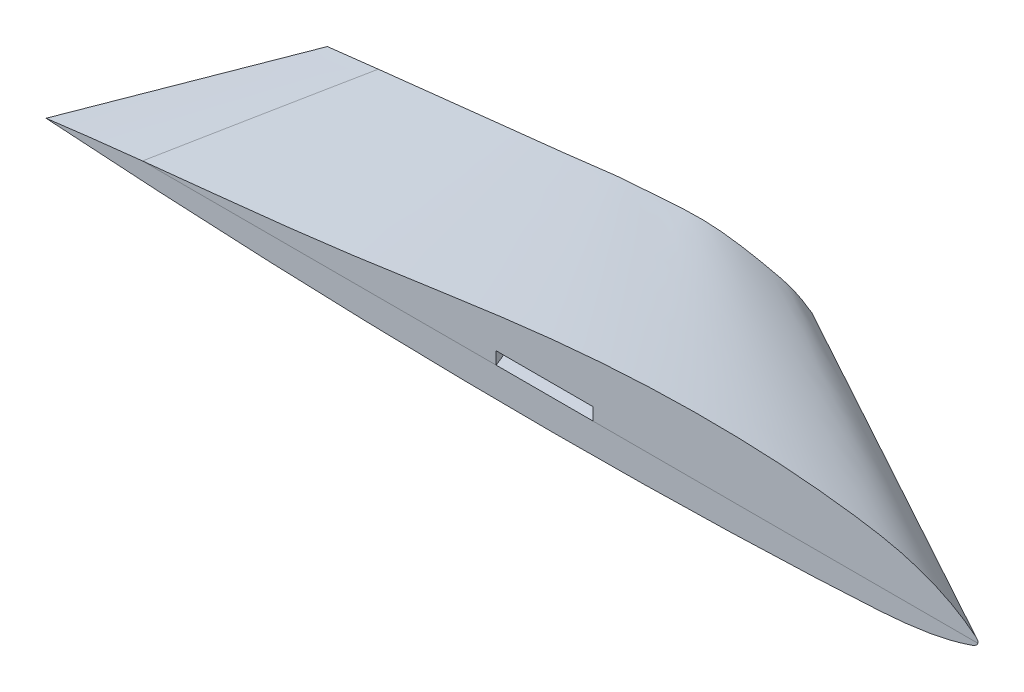
SolidWorks part; units mm, degrees
material "EPS 1.5lb"
ref_plane "Front Plane" through (0, 0, 0) normal (0, 0, 1) x (1, 0, 0)
ref_plane "Top Plane" through (0, 0, 0) normal (0, 1, 0) x (1, 0, 0)
ref_plane "Right Plane" through (0, 0, 0) normal (1, 0, 0) x (0, 0, -1)
sketch "Sketch1" plane through (0, 0, 0) normal (0, 0, 1) x (1, 0, 0)
  spline S3 degree 3 poles (-353.0971, 3.7664) (-263.6099, 15.4897) (-103.4056, 27.7025) (139.6254, 69.7319) (320.6009, 70.898) (447.0294, 49.1568) (484.462, 32.3978) (505.2254, 13.2914) knots 0 0 0 0 0.308402 0.542913 0.85017 0.887176 1 1 1 1
  spline S4 degree 3 poles (-353.0971, 3.7664) (-171.2042, -8.6227) (70.6812, -17.727) (367.6345, -8.5893) (467.935, -1.6347) (505.2254, 13.2914) knots 0 0 0 0 0.625313 0.861779 1 1 1 1
ref_plane "Plane1" through (0, 0, -180.975) normal (0, 0, 1) x (1, 0, 0)
sketch "Sketch2" plane through (0, 0, -180.975) normal (0, 0, 1) x (1, 0, 0)
  ellipse E1 centre (137.6249, -20.0426) end of major axis (189.6794, -20.0426) minor radius 48.2641 (175.2698, 13.2914) -> (153.373, 25.9598) ccw construction
  spline S0 degree 3 poles (-276.1301, 8.6931) (-231.4597, 13.8922) (-160.6069, 22.0458) (-55.2186, 32.8482) (-5.4847, 39.5878) (20.2948, 40.7341) (52.2153, 43.3112) (77.4334, 43.8548) (107.6579, 39.591) (131.1314, 34.7665) (149.4992, 30.2941) (163.4187, 23.0591) (171.5303, 16.9219) (175.2698, 13.2914) knots 0 0 0 0 0.247404 0.462109 0.504395 0.627983 0.653402 0.743134 0.818761 0.882434 0.92418 0.960505 1 1 1 1
  spline S4 degree 3 poles (-276.1301, 8.6931) (-174.261, 0.9112) (-23.6694, 0.6839) (127.5151, 0.6814) (175.2698, 13.2914) knots 0 0 0 0 0.676464 1 1 1 1
loft "Loft1" add profiles "Sketch1", "Sketch2" connector at (-353.0971, 3.7664, 0) connector at (-276.1301, 8.6931, -180.975)
fillet "Fillet1" radius 6.35 1 edges
ref_plane "Plane2" through (0, 19.812, 0) normal (0, 1, 0) x (1, 0, 0)
sketch "Sketch7" plane through (0, 19.812, 0) normal (0, 1, 0) x (1, 0, 0)
  line L0 (148.5529, 0) -> (75.4342, 180.975)
  line L1 (-13.4658, 180.975) -> (59.6529, 0)
  line L2 (59.6529, 0) -> (148.5529, 0)
  line L3 (75.4342, 180.975) -> (-13.4658, 180.975)
  line L5 (-44.6577, 180.975) -> (44.6577, 180.975) construction
  line L7 (-44.6562, 0) -> (44.6562, 0) construction
  dimension "D1" = 501.65
  dimension "D2" = 88.9
  dimension "D3" = 68
  dimension "D4" = 88.9
extrude "Cut-Extrude1" cut sketch "Sketch7" against normal mid plane 11.43
sketch "Sketch8" plane through (0, 19.812, 0) normal (0, 1, 0) x (1, 0, 0)
  line L0 (-276.1301, 180.975) -> (-353.0971, 0) construction
  line L2 (-328.3189, 58.2617) -> (-239.4979, 20.487)
  line L3 (-239.4979, 20.487) -> (-171.2438, 180.975)
  line L4 (-171.2438, 180.975) -> (-276.1301, 180.975)
  line L5 (167.9966, 180.975) -> (-276.1301, 180.975) construction
  line L6 (167.9966, 180.975) -> (-276.1301, 180.975) construction
  line L7 (-276.1301, 180.975) -> (-328.3189, 58.2617)
  dimension "D1" = 133.35
  dimension "D2" = 96.52
extrude "Cut-Extrude2" [suppressed] cut sketch "Sketch8" against normal through all and the other way through all
sketch "Sketch9" plane through (0, 0, 0) normal (0, 0, 1) x (1, 0, 0)
  line L0 (501.6041, 0) -> (501.407, 14.9983) construction
  line L1 (99.5364, 0) -> (-99.5364, 0) construction
  line L2 (501.407, 14.9983) -> (-353.0971, 3.7664) construction
  spline S0 degree 3 poles (495.958, 9.828) (496.8835, 10.1499) (497.7705, 10.5419) (499.008, 11.2994) (499.4048, 11.5805) (500.1496, 12.2315) (500.4885, 12.594) (500.9041, 13.2106) (501.0244, 13.4247) (501.2214, 13.8733) (501.2987, 14.1109) (501.3955, 14.5963) (501.415, 14.8413) (501.3938, 15.3365) (501.3526, 15.5828) (501.2176, 16.0565) (501.1224, 16.2887) (500.8939, 16.7255) (500.7606, 16.9316) (500.4639, 17.3241) (500.2996, 17.5112) (499.9516, 17.8629) (499.7676, 18.0283) (499.5755, 18.185) knots 0 0 0 0 0.25 0.25 0.375 0.375 0.5 0.5 0.5625 0.5625 0.625 0.625 0.6875 0.6875 0.75 0.75 0.8125 0.8125 0.875 0.875 0.9375 0.9375 1 1 1 1 construction
sketch "Sketch10" plane through (0, 0, -180.975) normal (0, 0, -1) x (-1, 0, 0)
  line L0 (-170.4193, 0) -> (-170.1582, 15.9838) construction
  line L1 (-170.1582, 15.9838) -> (276.1301, 8.6931) construction
  line L2 (99.5364, 0) -> (-99.5364, 0) construction
  spline S1 degree 3 poles (-167.9966, 19.4182) (-168.2414, 19.238) (-168.4753, 19.0462) (-168.9159, 18.6336) (-169.1233, 18.4121) (-169.4986, 17.9328) (-169.663, 17.6797) (-169.932, 17.1385) (-170.0362, 16.8477) (-170.1566, 16.2561) (-170.1738, 15.9468) (-170.1306, 15.4957) (-170.1051, 15.347) (-170.0331, 15.0527) (-169.9861, 14.9062) (-169.8194, 14.4828) (-169.6742, 14.2186) (-169.3313, 13.7181) (-169.1348, 13.4845) (-168.7149, 13.0536) (-168.4897, 12.8542) (-168.0156, 12.4801) (-167.766, 12.3054) (-167.003, 11.8211) (-166.4706, 11.5466) (-165.3734, 11.0635) (-164.8067, 10.855) (-163.6551, 10.494) (-163.0716, 10.3417) (-162.4816, 10.2129) knots 0 0 0 0 0.0625 0.0625 0.125 0.125 0.1875 0.1875 0.25 0.25 0.3125 0.3125 0.34375 0.34375 0.375 0.375 0.4375 0.4375 0.5 0.5 0.5625 0.5625 0.625 0.625 0.75 0.75 0.875 0.875 1 1 1 1 construction
ref_plane "Plane3" through (0, 14.097, 0) normal (0, 1, 0) x (1, 0, 0)
split "Split1" trim tools "Plane3" bodies to split 104 resulting bodies 107 108
